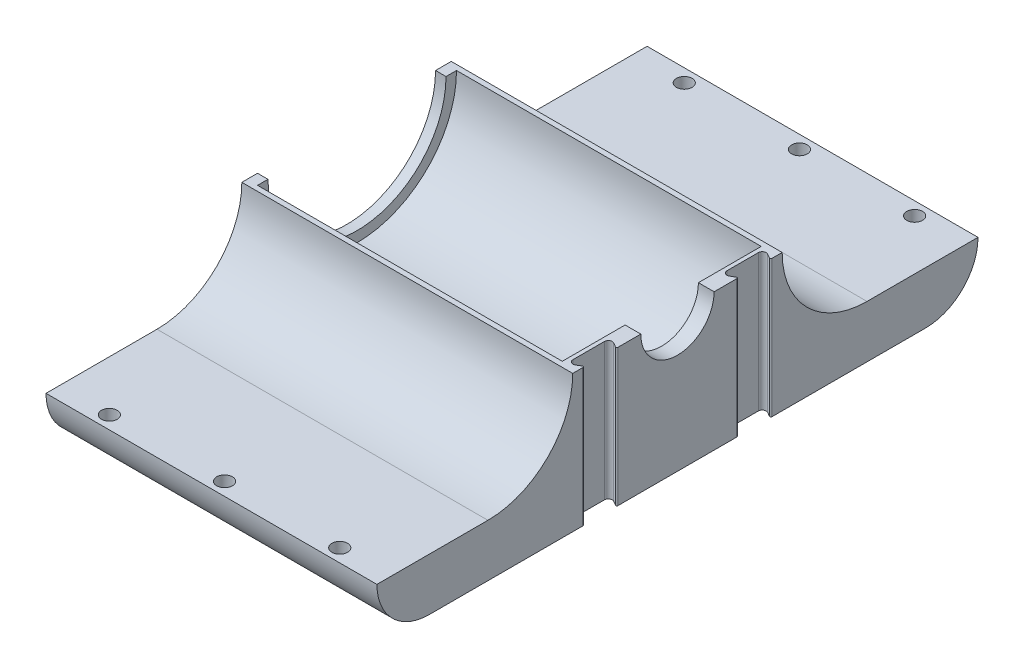
SolidWorks part; units mm, degrees
ref_plane "Front Plane" through (0, 0, 0) normal (0, 0, 1) x (1, 0, 0)
ref_plane "Top Plane" through (0, 0, 0) normal (0, 1, 0) x (1, 0, 0)
ref_plane "Right Plane" through (0, 0, 0) normal (1, 0, 0) x (0, 0, -1)
sketch "Sketch1" plane through (0, 0, 0) normal (1, 0, 0) x (0, 0, -1)
  line L0 (57.4, 42.0261) -> (57.4, 0) construction
  line L1 (0, 0) -> (114.8, 0)
  line L2 (0, 0) -> (0, 26.2)
  line L3 (114.8, 0) -> (114.8, 26.2)
  line L4 (0, 26.2) -> (5, 26.2) construction
  line L6 (37.4, 26.2) -> (77.4, 26.2) construction
  line L7 (37.4, 26.2) -> (77.4, 26.2)
  line L8 (0, 26.2) -> (5, 26.2)
  line L10 (37.4, 26.2) -> (77.4, 26.2)
  line L11 (109.8, 26.2) -> (114.8, 26.2)
  arc A0 (5, 26.2) -> (37.4, 26.2) centre (21.2, 26.2) ccw
  arc A1 (77.4, 26.2) -> (109.8, 26.2) centre (93.6, 26.2) ccw
  circle A2 centre (57.4, 13.245) radius 62.5 construction
  point P15 (93.6, 10)
  dimension "D4" = 16.2
  dimension "D3" = 16.2
  dimension "D6" = 125
  dimension "D1" = 5
  dimension "D5" = 10
  dimension "D2" = 40
extrude "Boss-Extrude1" add sketch "Sketch1" along normal blind 63.2 contours L8 L2 L1 L3 L7 region at (0, 10.7494, -57.4)
sketch "Sketch30" plane through (0, 26.2, 0) normal (0, 1, 0) x (1, 0, 0)
  line L0 (63.2, 57.4) -> (17.5829, 57.4) construction
  line L1 (63.2, 37.4) -> (63.2, 77.4) construction
  line L2 (63.2, 75.101) -> (60.95, 76.4)
  line L3 (60.95, 76.4) -> (60.95, 67.8019)
  line L4 (60.95, 67.8019) -> (63.2, 69.101)
  line L5 (63.2, 45.699) -> (60.95, 46.9981)
  line L6 (60.95, 46.9981) -> (60.95, 38.4)
  line L7 (60.95, 38.4) -> (63.2, 39.699)
  line L8 (63.2, 75.101) -> (63.2, 69.101)
  line L9 (63.2, 45.699) -> (63.2, 39.699)
  line L10 (63.2, 77.4) -> (0, 77.4) construction
  line L12 (63.2, 37.4) -> (0, 37.4) construction
  dimension "D1" = 6
  dimension "D2" = 60
  dimension "D3" = 60
  dimension "D4" = 2.25
  dimension "D5" = 60
  dimension "D6" = 1
  dimension "D7" = 1
extrude "Cut-Extrude14" cut sketch "Sketch30" against normal up to next
sketch "Sketch31" plane through (0, 0, 0) normal (-1, 0, 0) x (0, 0, 1)
  line L0 (-37.4, 26.2) -> (-77.4, 26.2) construction
  circle A0 centre (-57.4, 26.2) radius 19
  dimension "D1" = 38
extrude "Cut-Extrude15" cut sketch "Sketch31" against normal offset from surface (60.2 mm away) 3 contours A0 up to face at (63.2, 13.1, -57.4)
sketch "Sketch32" plane through (63.2, 0, 0) normal (1, 0, 0) x (0, 0, -1)
  line L0 (45.699, 26.2) -> (69.101, 26.2) construction
  circle A0 centre (57.4, 26.2) radius 7
  dimension "D1" = 14
extrude "Cut-Extrude16" cut sketch "Sketch32" against normal up to next
sketch "Sketch33" plane through (0, 0, 0) normal (-1, 0, 0) x (0, 0, 1)
  line L0 (-74.4, 26.2) -> (-76.4, 26.2)
  line L1 (-40.4, 26.2) -> (-38.4, 26.2)
  arc A1 (-76.4, 26.2) -> (-38.4, 26.2) centre (-57.4, 26.2) ccw construction
  arc A2 (-74.4, 26.2) -> (-40.4, 26.2) centre (-57.4, 26.2) ccw
  arc A3 (-74.4, 26.2) -> (-40.4, 26.2) centre (-57.4, 26.2) ccw
  arc A4 (-76.4, 26.2) -> (-38.4, 26.2) centre (-57.4, 26.2) ccw
  dimension "D1" = 2
extrude "Boss-Extrude6" add sketch "Sketch33" against normal blind 2
fillet "Fillet1" radius 10 2 edges at (31.6, 0, -114.8) (31.6, 0, 0)
sketch "Sketch34" plane through (0, 26.2, 0) normal (0, 1, 0) x (1, 0, 0)
  line L0 (0, 112.3) -> (63.2, 112.3) construction
  line L1 (0, 109.8) -> (0, 114.8) construction
  line L2 (63.2, 109.8) -> (63.2, 114.8) construction
  line L3 (63.2, 57.4) -> (76.2618, 57.4) construction
  line L4 (63.2, 50.4) -> (63.2, 64.4) construction
  circle A0 centre (9.6, 112.3) radius 1.5
  circle A1 centre (31.6, 112.3) radius 1.5
  circle A2 centre (53.6, 112.3) radius 1.5
  circle A3 centre (53.6, 2.5) radius 1.5
  circle A4 centre (31.6, 2.5) radius 1.5
  circle A5 centre (9.6, 2.5) radius 1.5
  dimension "D1" = 3
  dimension "D2" = 22
  dimension "D3" = 22
extrude "Cut-Extrude17" cut sketch "Sketch34" against normal blind 20
sketch "Sketch35" plane through (0, 0, 0) normal (0, -1, 0) x (1, 0, 0)
  line L0 (31.6, -10) -> (31.6, -104.8) construction
  line L1 (16.35, -29.9) -> (46.85, -29.9) construction
  line L2 (16.35, -29.9) -> (16.35, -84.9) construction
  line L3 (16.35, -84.9) -> (46.85, -84.9) construction
  line L4 (46.85, -29.9) -> (46.85, -84.9) construction
  line L5 (63.2, -10) -> (0, -10) construction
  line L6 (0, -104.8) -> (63.2, -104.8) construction
  line L10 (16.35, -57.4) -> (0, -57.4) construction
  line L11 (0, -10) -> (0, -104.8) construction
  circle A0 centre (16.35, -29.9) radius 2.3
  circle A1 centre (46.85, -29.9) radius 2.3
  circle A2 centre (16.35, -84.9) radius 2.3
  circle A3 centre (46.85, -84.9) radius 2.3
  point P8 (31.6, -29.9)
  dimension "D1" = 4.6
  dimension "D2" = 4.6
  dimension "D3" = 4.6
  dimension "D4" = 4.6
  dimension "D5" = 55
  dimension "D6" = 30.5
extrude "Cut-Extrude18" cut sketch "Sketch35" against normal blind 6
sketch "Sketch36" plane through (63.2, 0, 0) normal (1, 0, 0) x (0, 0, -1)
  line L0 (21.2, 10) -> (0, 10)
  line L1 (0, 10) -> (0, 26.2)
  line L2 (0, 26.2) -> (5, 26.2)
  line L3 (0, 26.2) -> (5, 26.2) construction
  line L4 (57.4, 19.2) -> (57.4, 39.0886) construction
  line L5 (114.8, 26.2) -> (109.8, 26.2)
  line L6 (114.8, 10) -> (114.8, 26.2)
  line L7 (93.6, 10) -> (114.8, 10)
  arc A0 (5, 26.2) -> (37.4, 26.2) centre (21.2, 26.2) ccw construction
  arc A1 (5, 26.2) -> (21.2, 10) centre (21.2, 26.2) ccw
  arc A2 (50.4, 26.2) -> (64.4, 26.2) centre (57.4, 26.2) ccw construction
  arc A3 (109.8, 26.2) -> (93.6, 10) centre (93.6, 26.2) cw
extrude "Cut-Extrude19" cut sketch "Sketch36" against normal up to next
fillet "Fillet2" radius 0.75 4 edges at (60.95, 13.1, -38.4) (60.95, 13.1, -46.9981) (60.95, 13.1, -67.8019) (60.95, 13.1, -76.4)
fillet "Fillet4" radius 0.2 4 edges at (63.2, 13.1, -75.101) (63.2, 13.1, -69.101) (63.2, 13.1, -45.699) (63.2, 13.1, -39.699)
equation "\"MotorDIA\"= 37' Motor Diameter"
equation "\"SyringeDIA\"= 31.4'60ml Syringe Diameter"
equation "\"MotorShaftDIA\"= 6'Motor Shaft Dia"
equation "\"MotorKeyway\"= 1'Motor Shaft Keyway Depth"
equation "\"MotorLength\"= 56.7'Motor Length Excluding Shaft"
equation "\"SyringeLength\"= 117.3'60ml Syringe Length Excluding Nozzle"
equation "\"3Dtol\"= .5'Sizing Tolerance for 3D printed parts"
equation "\"ChamberDIA\"= 100 - 4'Buoyancy Chamber inner Diameter"
equation "\"ChamberThk\"= 2mm'Buoyancy Chamber Wall Thickness"
equation "\"D1@Boss-Extrude1\"=\"MotorLength\"+\"3Dtol\"+4"
equation "\"BearingOD\"= 10"
equation "\"BearingID\"= 4"
equation "\"Bearingwidth\"= 4"
equation "\"ShaftDIA\"= 4"
equation "\"D3@Sketch1\"=\"D4@Sketch1\""
